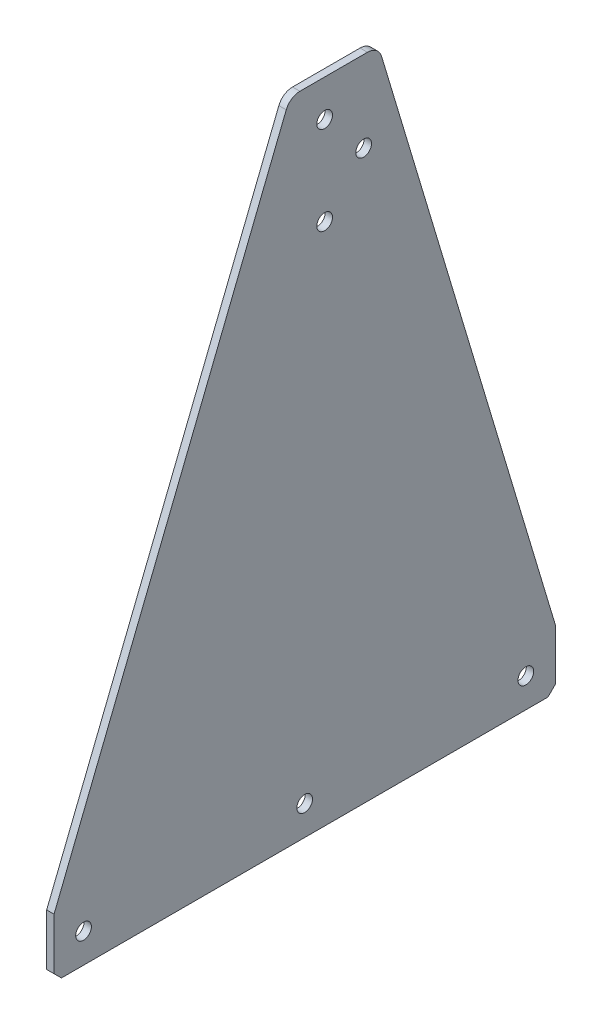
SolidWorks part; units mm, degrees
material "6061-T6 (SS)"
ref_plane "Front Plane" through (0, 0, 0) normal (0, 0, 1) x (1, 0, 0)
ref_plane "Top Plane" through (0, 0, 0) normal (0, 1, 0) x (1, 0, 0)
ref_plane "Right Plane" through (0, 0, 0) normal (1, 0, 0) x (0, 0, -1)
sketch "Sketch1" plane through (0, 0, 0) normal (1, 0, 0) x (0, 0, -1)
  line L1 (105.8992, 279.4) -> (134.9754, 279.4)
  line L2 (141.0576, 274.8747) -> (215.9, 25.4)
  line L3 (215.9, 25.4) -> (215.9, 0)
  line L4 (215.9, 0) -> (0, 0)
  line L5 (0, 25.4) -> (0, 0)
  line L6 (100.0033, 275.4083) -> (0, 25.4)
  arc A0 (100.0033, 275.4083) -> (105.8992, 279.4) centre (105.8992, 273.05) cw
  arc A1 (134.9754, 279.4) -> (141.0576, 274.8747) centre (134.9754, 273.05) cw
  point P2 (101.6, 279.4)
  point P12 (139.7, 279.4)
  dimension "D4" = 6.35
  dimension "D1" = 101.6
  dimension "D2" = 279.4
  dimension "D3" = 215.9
  dimension "D5" = 25.4
  dimension "D6" = 76.2
extrude "Boss-Extrude1" add sketch "Sketch1" along normal blind 3.175
sketch "Sketch2" [suppressed] plane through (3.175, 0, 0) normal (1, 0, 0) x (0, 0, -1)
  line L0 (-279.4, 0) -> (279.4, 0) construction
  line L1 (254, 0) -> (228.6, 0)
  line L2 (254, 0) -> (254, 19.05)
  line L3 (247.65, 25.4) -> (234.95, 25.4)
  line L4 (228.6, 0) -> (228.6, 19.05)
  line L6 (203.2, 0) -> (177.8, 0)
  line L7 (203.2, 0) -> (203.2, 19.05)
  line L8 (196.85, 25.4) -> (184.15, 25.4)
  line L9 (177.8, 0) -> (177.8, 19.05)
  line L10 (152.4, 0) -> (127, 0)
  line L11 (152.4, 0) -> (152.4, 19.05)
  line L12 (146.05, 25.4) -> (133.35, 25.4)
  line L13 (127, 0) -> (127, 19.05)
  line L14 (101.6, 0) -> (76.2, 0)
  line L15 (101.6, 0) -> (101.6, 19.05)
  line L16 (95.25, 25.4) -> (82.55, 25.4)
  line L17 (76.2, 0) -> (76.2, 19.05)
  line L18 (50.8, 0) -> (25.4, 0)
  line L19 (50.8, 0) -> (50.8, 19.05)
  line L20 (44.45, 25.4) -> (31.75, 25.4)
  line L21 (25.4, 0) -> (25.4, 19.05)
  line L22 (50.8, 0) -> (76.2, 0) construction
  line L23 (101.6, 0) -> (127, 0) construction
  line L24 (152.4, 0) -> (177.8, 0) construction
  line L25 (203.2, 0) -> (228.6, 0) construction
  line L27 (279.4, 0) -> (279.4, 12.7) construction
  line L28 (0, 609.6) -> (0, 0) construction
  arc A0 (31.75, 25.4) -> (25.4, 19.05) centre (31.75, 19.05) ccw
  arc A1 (50.8, 19.05) -> (44.45, 25.4) centre (44.45, 19.05) ccw
  arc A2 (82.55, 25.4) -> (76.2, 19.05) centre (82.55, 19.05) ccw
  arc A3 (101.6, 19.05) -> (95.25, 25.4) centre (95.25, 19.05) ccw
  arc A4 (133.35, 25.4) -> (127, 19.05) centre (133.35, 19.05) ccw
  arc A5 (152.4, 19.05) -> (146.05, 25.4) centre (146.05, 19.05) ccw
  arc A6 (184.15, 25.4) -> (177.8, 19.05) centre (184.15, 19.05) ccw
  arc A7 (203.2, 19.05) -> (196.85, 25.4) centre (196.85, 19.05) ccw
  arc A8 (234.95, 25.4) -> (228.6, 19.05) centre (234.95, 19.05) ccw
  arc A9 (254, 19.05) -> (247.65, 25.4) centre (247.65, 19.05) ccw
  point P52 (254, 25.4)
  dimension "D5" = 6.35
  dimension "D1" = 25.4
  dimension "D2" = 25.4
  dimension "D3" = 25.4
  dimension "D4" = 25.4
extrude "Cut-Extrude1" [suppressed] cut sketch "Sketch2" against normal through all
sketch "Sketch3" plane through (3.175, 0, 0) normal (1, 0, 0) x (0, 0, -1)
  line L0 (0, 0) -> (215.9, 0) construction
  line L3 (215.9, 0) -> (215.9, 25.4) construction
  circle A0 centre (133.35, 244.475) radius 3.3782
  circle A1 centre (116.5495, 225.425) radius 3.3782
  circle A2 centre (116.5495, 263.525) radius 3.3782
  dimension "D1" = 6.7564
  dimension "D2" = 244.475
  dimension "D3" = 82.55
  dimension "D4" = 25.4
  dimension "D5" = 25.4
  dimension "D6" = 38.1
extrude "Cut-Extrude2" cut sketch "Sketch3" against normal through all
sketch "Sketch4" plane through (3.175, 0, 0) normal (1, 0, 0) x (0, 0, -1)
  line L0 (0, 0) -> (215.9, 0) construction
  line L1 (0, 25.4) -> (0, 0) construction
  line L2 (215.9, 0) -> (215.9, 25.4) construction
  line L3 (12.7, 12.7) -> (203.2, 12.7) construction
  circle A0 centre (12.7, 12.7) radius 3.3782
  circle A1 centre (107.95, 12.7) radius 3.3782
  circle A2 centre (203.2, 12.7) radius 3.3782
  dimension "D1" = 12.7
  dimension "D2" = 12.7
  dimension "D3" = 12.7
  dimension "D4" = 6.7564
extrude "Cut-Extrude3" cut sketch "Sketch4" against normal through all
chamfer "Chamfer1" distance 3.175 angle 45 2 edges at (1.5875, 0, 0) (1.5875, 0, -215.9)
